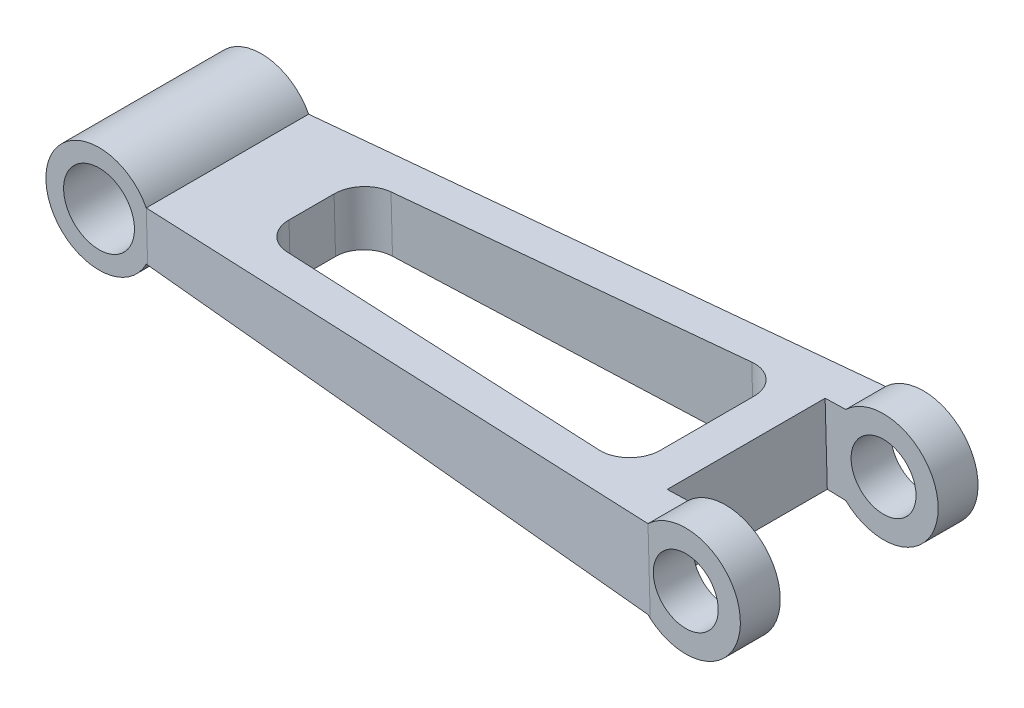
SolidWorks part; units mm, degrees
ref_plane "Front Plane" through (0, 0, 0) normal (0, 0, 1) x (1, 0, 0)
ref_plane "Top Plane" through (0, 0, 0) normal (0, 1, 0) x (1, 0, 0)
ref_plane "Right Plane" through (0, 0, 0) normal (1, 0, 0) x (0, 0, -1)
sketch "Sketch1" plane through (0, 0, 0) normal (0, 0, 1) x (1, 0, 0)
  line L0 (0, 0) -> (-211.5, 0)
  line L1 (0, 0) -> (211.5, 0)
  line L2 (0, 0) -> (0, 148.1639)
  line L4 (174.5, 0) -> (174.5, 27)
  line L7 (-179.512, 16.5156) -> (185.9135, 26.7269)
  line L8 (-179.512, -16.5156) -> (185.9135, -26.7269)
  circle A0 centre (-211.5, 0) radius 36
  circle A1 centre (-211.5, 0) radius 24
  circle A2 centre (211.5, 0) radius 22
  circle A3 centre (211.5, 0) radius 37
  dimension "D3" = 72
  dimension "D4" = 48
  dimension "D5" = 74
  dimension "D6" = 44
  dimension "D8" = 27
  dimension "D1" = 211.5
  dimension "D2" = 211.5
extrude "Boss-Extrude1" add sketch "Sketch1" against normal blind 161 contours A1 A0 | A0 L0 L2 L7 | L8 A3 L1 L0 A0 | L7 L2 L1 L4 | A3 A2 | L4 A3 L7 region at (14.2163, -11.06, 0) region at (90.2082, 12.0263, 0) region at (-84.5904, 9.6111, 0) region at (-177.5068, -8.2576, 0) region at (177.7999, 20.1441, 0) region at (178.4352, 14.12, 0)
sketch "Sketch3" plane through (-0.6012, 21.515, 0) normal (-0.0279, 0.9996, 0) x (0.9996, 0.0279, 0)
  line L1 (-178.9806, 161) -> (-178.9806, 0) construction
  line L2 (-178.9806, 135.5) -> (-268.8401, 135.5)
  line L4 (186.5875, 161) -> (186.5875, 0) construction
  line L5 (186.5875, 161) -> (-178.9806, 135.5)
  line L7 (-178.9806, 25.5) -> (-268.8401, 25.5)
  line L8 (186.5875, 0) -> (-178.9806, 25.5)
  line L9 (-268.8401, 135.5) -> (-268.8401, 212.5713)
  line L10 (-268.8401, 212.5713) -> (186.5875, 212.5713)
  line L11 (186.5875, 212.5713) -> (186.5875, 161)
  line L12 (-268.8401, 25.5) -> (-268.8401, -47.6374)
  line L13 (-268.8401, -47.6374) -> (186.5875, -47.6374)
  line L14 (186.5875, -47.6374) -> (186.5875, 0)
extrude "Cut-Extrude1" cut sketch "Sketch3" against normal blind 161 and the other way blind 161
sketch "Sketch4" plane through (-0.6012, 21.515, 0) normal (-0.0279, 0.9996, 0) x (0.9996, 0.0279, 0)
  line L4 (-121.9806, 65.2383) -> (-121.9806, 95.7617)
  line L5 (-177.2409, 110.5606) -> (188.3271, 136.0606)
  line L6 (-103.3723, 115.7133) -> (125.1958, 131.6569)
  line L7 (-103.4571, 45.2928) -> (125.111, 28.3726)
  line L10 (146.5875, 161) -> (146.5875, 0)
  line L11 (146.5875, 111.7054) -> (146.5875, 48.318)
  arc A0 (125.111, 28.3726) -> (146.5875, 48.318) centre (126.5875, 48.318) ccw
  arc A1 (146.5875, 111.7054) -> (125.1958, 131.6569) centre (126.5875, 111.7054) ccw
  arc A2 (-121.9806, 65.2383) -> (-103.4571, 45.2928) centre (-101.9806, 65.2383) ccw
  arc A3 (-103.3723, 115.7133) -> (-121.9806, 95.7617) centre (-101.9806, 95.7617) ccw
  dimension "D2" = 25
  dimension "D1" = 20
  dimension "D4" = 40
extrude "Cut-Extrude2" cut sketch "Sketch4" against normal blind 161
sketch "Sketch6" plane through (-0.6012, 21.515, 0) normal (-0.0279, 0.9996, 0) x (0.9996, 0.0279, 0)
  line L1 (172.5875, 80.0117) -> (172.5875, 133.9887)
  line L2 (172.5875, 133.9887) -> (279.946, 133.9887)
  line L3 (279.946, 133.9887) -> (279.946, 27.0052)
  line L4 (279.946, 27.0052) -> (172.5875, 27.0052)
  line L5 (172.5875, 27.0052) -> (172.5875, 80.0117)
extrude "Cut-Extrude3" cut sketch "Sketch6" against normal blind 161 and the other way blind 161
